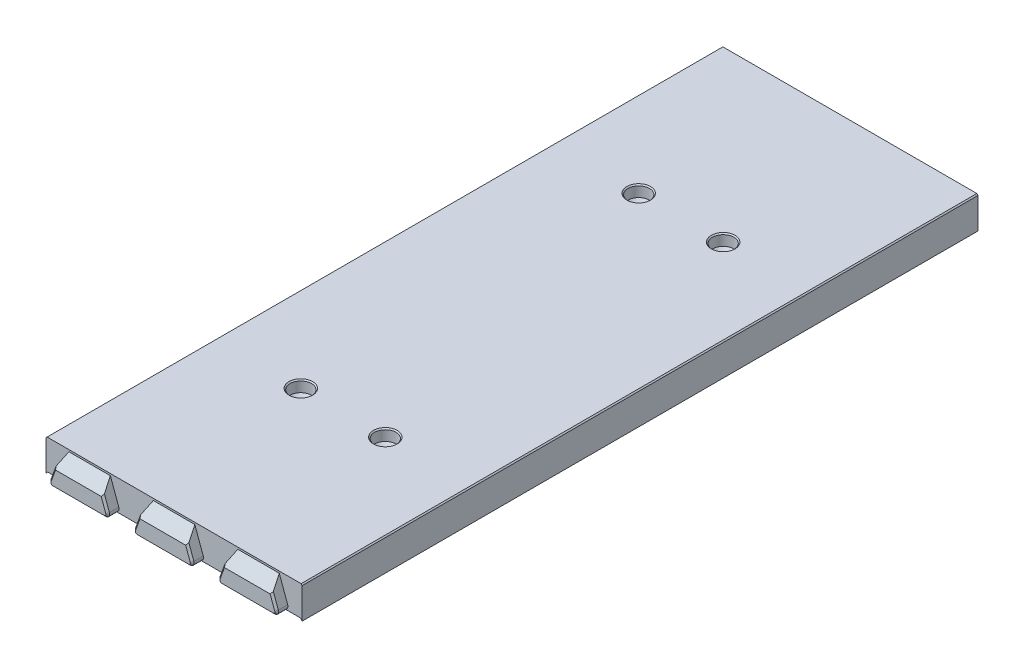
SolidWorks part; units mm, degrees
ref_plane "Front Plane" through (0, 0, 0) normal (0, 0, 1) x (1, 0, 0)
ref_plane "Top Plane" through (0, 0, 0) normal (0, 1, 0) x (1, 0, 0)
ref_plane "Right Plane" through (0, 0, 0) normal (1, 0, 0) x (0, 0, -1)
sketch "Sketch1" plane through (0, 0, 0) normal (0, 0, 1) x (1, 0, 0)
  line L0 (0, 0) -> (0, 8) construction
  line L1 (-34.125, 0) -> (0, 0) construction
  line L2 (-34.125, 0) -> (-34.125, 8)
  line L3 (-34.125, 8) -> (34.125, 8)
  line L5 (-34.125, 0) -> (-32.125, 0)
  line L6 (-32.125, 0) -> (-32.125, 6)
  line L7 (-32.125, 6) -> (32.125, 6)
  line L9 (32.125, 0) -> (32.125, 6)
  line L10 (34.125, 0) -> (32.125, 0)
  line L11 (34.125, 0) -> (34.125, 8)
  point P8 (0, 6)
  dimension "D2" = 6
  dimension "D1" = 34.125
  dimension "D3" = 2
  dimension "D4" = 2
extrude "Boss-Extrude1" add sketch "Sketch1" against normal blind 90
sketch "Sketch7" plane through (0, 0, 0) normal (0, 0, 1) x (1, 0, 0)
  line L2 (-32.125, 0) -> (32.125, 0)
  line L13 (-32.125, 0) -> (-32.125, 6)
  line L15 (-32.125, 6) -> (32.125, 6)
  line L16 (32.125, 0) -> (32.125, 6)
  line M3 (-32.125, 0) -> (-32.125, 6)
  line M4 (-32.125, 6) -> (32.125, 6)
  line M5 (32.125, 6) -> (32.125, 0)
extrude "Boss-Extrude7" add sketch "Sketch7" against normal blind 1 contours M4 M3 | M5 region at (0, 3, 0)
sketch "Sketch2" plane through (0, 0, 0) normal (0, 0, 1) x (1, 0, 0)
  line L14 (17.1618, 8) -> (14.25, 0)
  line L15 (34.125, 8) -> (-34.125, 8) construction
  line L16 (-34.125, 0) -> (34.125, 0) construction
  line L17 (14.25, 0) -> (30.75, 0)
  line L18 (17.1618, 8) -> (27.8382, 8)
  line L19 (-34.125, 0) -> (34.125, 0) construction
  line L21 (27.8382, 8) -> (30.75, 0)
  line L24 (11.25, 0) -> (11.25, 8) construction
  line L27 (-5.3382, 8) -> (-8.25, 0)
  line L28 (-5.3382, 8) -> (5.3382, 8)
  line L29 (-8.25, 0) -> (8.25, 0)
  line L30 (5.3382, 8) -> (8.25, 0)
  line L31 (-27.8382, 8) -> (-30.75, 0)
  line L32 (-27.8382, 8) -> (-17.1618, 8)
  line L33 (-30.75, 0) -> (-14.25, 0)
  line L34 (-17.1618, 8) -> (-14.25, 0)
  line L39 (17.1618, 8) -> (-5.3382, 8) construction
  line L40 (33.75, 8) -> (33.75, 0) construction
  line L41 (34.125, 0) -> (34.125, 8) construction
  line L42 (-33.75, 8) -> (-33.75, 0) construction
  line L43 (-34.125, 8) -> (-34.125, 0) construction
  point P22 (22.5, 8)
  point P23 (0, 8)
  dimension "D1" = 70
  dimension "D2" = 0.375
  dimension "D3" = 3
  dimension "D4" = 3
  dimension "D5" = 70
  dimension "D7" = 22.5
  dimension "D8" = 22.5
  dimension "D9" = 0.375
  dimension "D11" = 8
  dimension "D6" = 3
extrude "Boss-Extrude4" add sketch "Sketch2" along normal blind 3
sketch "Sketch8" plane through (0, 0, 0) normal (0, -1, 0) x (1, 0, 0)
  line L0 (-34.125, -22.5) -> (34.125, -22.5) construction
  line L1 (-32.6, -24.7417) -> (-32.6, -20.2583)
  line L2 (34.125, -90) -> (34.125, 0) construction
  line L3 (-34.125, 0) -> (-30.75, 0) construction
  line L4 (-32.75, -24.9559) -> (-32.75, -20.0441) construction
  line L5 (-32.75, -20.0441) -> (-28.75, -21.5) construction
  line L6 (-28.75, -21.5) -> (-28.75, -23.5) construction
  line L7 (-32.75, -90) -> (-32.75, -87.5441) construction
  line L8 (-32.75, -87.5441) -> (-28.75, -89) construction
  line L9 (-28.75, -89) -> (-28.75, -90) construction
  line L10 (-32.125, -90) -> (32.125, -90) construction
  line L11 (-28.75, -90) -> (-32.75, -90) construction
  line L12 (-32.75, -24.9559) -> (-28.75, -23.5) construction
  line L13 (0, -90) -> (0, 0) construction
  line L22 (-32.6, -20.2583) -> (-28.9, -21.605)
  line L23 (-34.125, -90) -> (-34.125, 0) construction
  line L28 (-34.125, -90) -> (-32.125, -90) construction
  line L29 (-28.9, -21.605) -> (-28.9, -23.395)
  line L30 (-32.6, -24.7417) -> (-28.9, -23.395)
  line L31 (-32.6, -89.85) -> (-32.6, -87.7583)
  line L32 (-32.6, -87.7583) -> (-28.9, -89.105)
  line L33 (-28.9, -89.105) -> (-28.9, -89.85)
  line L34 (-28.9, -89.85) -> (-32.6, -89.85) construction
  line L35 (-32.6, -89.85) -> (-32.6, -90)
  line L36 (-32.6, -90) -> (-28.9, -90)
  line L37 (-28.9, -90) -> (-28.9, -89.85)
  line L38 (32.6, -24.7417) -> (28.9, -23.395)
  line L39 (28.9, -21.605) -> (28.9, -23.395)
  line L40 (32.6, -20.2583) -> (28.9, -21.605)
  line L41 (32.6, -24.7417) -> (32.6, -20.2583)
  line L42 (32.6, -89.85) -> (32.6, -90)
  line L43 (32.6, -89.85) -> (32.6, -87.7583)
  line L44 (32.6, -87.7583) -> (28.9, -89.105)
  line L45 (28.9, -90) -> (28.9, -89.85)
  line L46 (32.6, -90) -> (28.9, -90)
  line L47 (28.9, -89.105) -> (28.9, -89.85)
  point P19 (-28.75, -22.5)
  dimension "D1" = 22.5
  dimension "D2" = 0.15
  dimension "D3" = 70
  dimension "D4" = 4
  dimension "D5" = 1.375
  dimension "D6" = 4
  dimension "D7" = 70
  dimension "D8" = 1
  dimension "D9" = 1
  dimension "D10" = 0.15
extrude "Boss-Extrude8" add sketch "Sketch8" against normal up to next and the other way blind 2
chamfer "Chamfer4" distance 0.5 angle 45 14 edges at (-28.9, -2, -89.5525) (-32.6, -2, -22.5) (-30.75, -2, -20.9317) (-28.9, -2, -22.5) (-30.75, -2, -24.0683) (30.75, -2, -24.0683) (28.9, -2, -22.5) (30.75, -2, -20.9317) (32.6, -2, -22.5) (28.9, -2, -89.5525) (30.75, -2, -88.4317) (32.6, -2, -88.8792) (-30.75, -2, -88.4317) (-32.6, -2, -88.8792)
fillet "Fillet4" radius 1 6 edges at (30.75, 0, 1.5) (14.25, 0, 1.5) (8.25, 0, 1.5) (-8.25, 0, 1.5) (-14.25, 0, 1.5) (-30.75, 0, 1.5)
chamfer "Chamfer6" distance 0.5 angle 45 15 edges at (15.9501, 4.671, 3) (29.0499, 4.671, 3) (22.5, 0, 3) (-29.0499, 4.671, 3) (-22.5, 0, 3) (-15.9501, 4.671, 3) (-6.5499, 4.671, 3) (6.5499, 4.671, 3) (0, 0, 3) (-30.141, 0.4264, 3) (-14.859, 0.4264, 3) (-7.641, 0.4264, 3) (7.641, 0.4264, 3) (14.859, 0.4264, 3) (30.141, 0.4264, 3)
fillet "Fillet2" radius 2 23 edges at (0, 6, -1) (-32.125, 3, -1) (32.125, 6, -10.7156) (32.125, 3, -1) (-32.125, 6, -10.7156) (-28.9, 6, -89.5525) (-32.125, 3, -20.4312) (-30.5125, 6, -21.0181) (-28.9, 6, -22.5) (-30.5125, 6, -23.9819) (-32.125, 3, -87.9312) (-30.5125, 6, -88.5181) (28.9, 6, -89.5525) (30.5125, 6, -88.5181) (32.125, 3, -87.9312) (32.125, 3, -24.5688) (30.5125, 6, -23.9819) (28.9, 6, -22.5) (30.5125, 6, -21.0181) (32.125, 3, -20.4312) (32.125, 6, -56.25) (-32.125, 3, -24.5688) (-32.125, 6, -56.25)
mirror "Mirror2" about plane through (0, 0, -90) normal (0, 0, 1) of "Fillet4", "Boss-Extrude1", "Boss-Extrude7", "Boss-Extrude4", "Boss-Extrude8", "Chamfer4", "Fillet2", "Chamfer6"
sketch "Sketch9" plane through (0, 0, 0) normal (0, 1, 0) x (1, 0, 0)
  line L16 (0, 90) -> (0, 0) construction
  line L17 (-34.125, 90) -> (34.125, 90) construction
  line L20 (34.125, 180) -> (34.125, 0) construction
  line L21 (-34.125, 180) -> (-34.125, 0) construction
  circle A0 centre (-11.25, 45) radius 5
  circle A4 centre (11.25, 45) radius 5
  circle A5 centre (11.25, 135) radius 5
  circle A6 centre (-11.25, 135) radius 5
  dimension "D3" = 10
  dimension "D1" = 45
  dimension "D2" = 11.25
extrude "Boss-Extrude9" add sketch "Sketch9" along normal up to next
fillet "Fillet3" radius 3 4 edges at (-11.25, 6, -50) (-11.25, 6, -140) (11.25, 6, -140) (11.25, 6, -50)
sketch "Sketch10" plane through (0, 0, 0) normal (0, 1, 0) x (1, 0, 0)
  circle A1 centre (-11.25, 45) radius 1.85
  circle A4 centre (-11.25, 45) radius 5 construction
  circle A8 centre (-11.25, 45) radius 5 construction
  circle A12 centre (11.25, 45) radius 1.85
  circle A13 centre (11.25, 135) radius 1.85
  circle A14 centre (-11.25, 135) radius 1.85
  dimension "D1" = 3.7
extrude "Cut-Extrude2" cut sketch "Sketch10" along normal through all
sketch "Sketch11" plane through (0, 8, 0) normal (0, 1, 0) x (1, 0, 0)
  circle A0 centre (-11.25, 135) radius 2.85
  circle A1 centre (11.25, 135) radius 2.85
  circle A2 centre (11.25, 45) radius 2.85
  circle A3 centre (-11.25, 45) radius 2.85
  dimension "D1" = 5.7
extrude "Cut-Extrude3" cut sketch "Sketch11" against normal blind 3
chamfer "Chamfer7" distance 1 angle 45 4 edges at (-11.25, 5, -43.15) (-11.25, 5, -133.15) (11.25, 5, -133.15) (11.25, 5, -43.15)
sketch "Sketch12" plane through (0, 0, 0) normal (1, 0, 0) x (0, 0, -1)
  line L0 (0, 7.5) -> (-3, 4.5)
  line L1 (-3, 1.171) -> (-3, 8) construction
  line L2 (-3, 4.5) -> (-3, 7.5)
  line L3 (-3, 7.5) -> (0, 7.5) construction
  line L4 (90, 8) -> (90, 0) construction
  line L5 (180, 8) -> (0, 8) construction
  line L6 (180, 0) -> (0, 0) construction
  line L8 (183, 4.5) -> (183, 7.5)
  line L9 (180, 7.5) -> (183, 4.5)
  line L10 (0, 0) -> (0, 8) construction
  line L11 (-3, 8) -> (-2.5, 8) construction
  line L12 (-3, 7.5) -> (-3, 8)
  line L13 (-3, 8) -> (0, 8)
  line L14 (0, 8) -> (0, 7.5)
  line L15 (183, 7.5) -> (180, 7.5) construction
  line L16 (180, 8) -> (180, 7.5)
  line L17 (183, 8) -> (180, 8)
  line L18 (183, 7.5) -> (183, 8)
  dimension "D1" = 45
  dimension "D2" = 3
  dimension "D3" = 0.5
extrude "Cut-Extrude4" cut sketch "Sketch12" against normal through all both and the other way through all
sketch "Sketch13" plane through (0, 0, -180) normal (0, 0, -1) x (-1, 0, 0)
  line L0 (-33.625, 0) -> (-34.125, -0.5)
  line L1 (-29.3219, 0) -> (-34.125, 0) construction
  line L2 (-34.125, -0.5) -> (-34.125, 0)
  line L3 (-34.125, 0) -> (-33.625, 0)
  line L4 (0, 0) -> (0, 8) construction
  line L5 (-34.125, 8) -> (34.125, 8) construction
  line L6 (34.125, 0) -> (33.625, 0)
  line L7 (34.125, -0.5) -> (34.125, 0)
  line L8 (33.625, 0) -> (34.125, -0.5)
  dimension "D1" = 0.5
  dimension "D2" = 0.5
extrude "Boss-Extrude10" add sketch "Sketch13" against normal up to surface (180 mm away) up to face at (0, 3.072, 0)
chamfer "Chamfer8" distance 0.3 angle 45 6 edges at (-34.125, 8, -90) (34.125, 8, -90) (11.25, 8, -132.15) (-11.25, 8, -132.15) (11.25, 8, -42.15) (-11.25, 8, -42.15)
